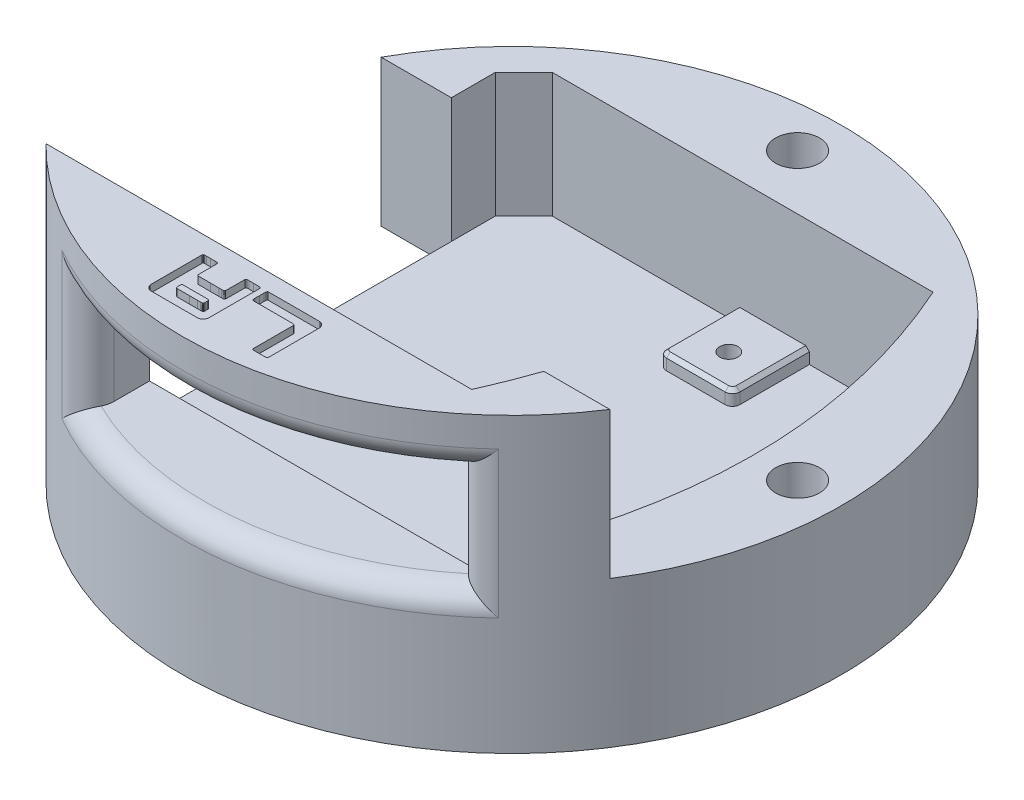
SolidWorks part; units mm, degrees
ref_plane "Plan de face" through (0, 0, 0) normal (0, 0, 1) x (1, 0, 0)
ref_plane "Plan de dessus" through (0, 0, 0) normal (0, 1, 0) x (1, 0, 0)
ref_plane "Plan de droite" through (0, 0, 0) normal (1, 0, 0) x (0, 0, -1)
sketch "Esquisse1" plane through (0, 0, 0) normal (0, 1, 0) x (1, 0, 0)
  circle A0 centre (0, 0) radius 45
  dimension "D1" = 90
extrude "Boss.-Extru.1" add sketch "Esquisse1" along normal blind 40
sketch "Esquisse2" plane through (0, 40, 0) normal (0, 1, 0) x (1, 0, 0)
  line L0 (-26, 31.5) -> (26, 31.5)
  line L1 (26, 0) -> (33, 0) construction
  line L2 (26, 31.5) -> (26, -31.5) construction
  line L3 (-26, 31.5) -> (-29.8891, 27.6109)
  line L4 (-29.8891, 27.6109) -> (-29.8891, 21.6109)
  line L5 (-29.8891, 21.6109) -> (-39.4711, 21.6109)
  line L6 (26, 0) -> (-63.3285, 0) construction
  line L7 (26, 31.5) -> (32.1364, 31.5) construction
  line L8 (-26, 31.5) -> (-32.1364, 31.5) construction
  line L9 (-29.8891, -21.6109) -> (-39.4711, -21.6109)
  line L10 (-29.8891, -27.6109) -> (-29.8891, -21.6109)
  line L11 (-26, -31.5) -> (-29.8891, -27.6109)
  line L12 (-26, -31.5) -> (26, -31.5)
  circle A0 centre (0, 0) radius 45 construction
  arc A1 (-39.4711, -21.6109) -> (-39.4711, 21.6109) centre (0, 0) cw
  spline S0 degree 2 poles (26, 31.5) (40, 0) (26, -31.5) knots 0 0 0 1 1 1
  circle M11 centre (0, 0) radius 45
  dimension "D1" = 52
  dimension "D2" = 7
  dimension "D3" = 63
  dimension "D4" = 135
  dimension "D5" = 5.5
  dimension "D6" = 6
extrude "Enlèv. mat.-Extru.1" cut sketch "Esquisse2" against normal offset from surface (37 mm away) 3 contours S0 L0 L3 L4 L5 L9 L10 L11 L12 M11 region at (-4.3513, 40, 0) up to face at (0, 0, 45)
sketch "Esquisse7" plane through (0, 3, 0) normal (0, 1, 0) x (1, 0, 0)
  line L0 (9.1109, 30) -> (-0.8891, 21) construction
  line L1 (9.1109, 30) -> (9.1109, 22)
  line L2 (8.1109, 21) -> (0.1109, 21)
  line L3 (-0.8891, 30) -> (-0.8891, 22)
  line L4 (-0.8891, 30) -> (9.1109, 30) construction
  line L5 (-0.8891, 30) -> (-0.8891, 31.5)
  line L6 (-0.8891, 31.5) -> (9.1109, 31.5)
  line L7 (9.1109, 30) -> (9.1109, 31.5)
  line L8 (-34.6801, 0) -> (18.839, 0) construction
  line L9 (9.1109, -30) -> (-0.8891, -21) construction
  line L10 (9.1109, -30) -> (9.1109, -31.5)
  line L11 (-0.8891, -31.5) -> (9.1109, -31.5)
  line L12 (-0.8891, -30) -> (-0.8891, -31.5)
  line L13 (-0.8891, -30) -> (-0.8891, -22)
  line L14 (8.1109, -21) -> (0.1109, -21)
  line L15 (9.1109, -30) -> (9.1109, -22)
  line L16 (-34.6801, 21.6109) -> (-34.6801, -21.6109) construction
  line L17 (-26, 31.5) -> (26, 31.5) construction
  line L18 (-29.8891, 21.6109) -> (-39.4711, 21.6109) construction
  arc A0 (0.1109, 21) -> (-0.8891, 22) centre (0.1109, 22) cw
  arc A1 (9.1109, 22) -> (8.1109, 21) centre (8.1109, 22) cw
  arc A2 (9.1109, -22) -> (8.1109, -21) centre (8.1109, -22) ccw
  arc A3 (0.1109, -21) -> (-0.8891, -22) centre (0.1109, -22) ccw
  point P26 (-34.6801, 0)
  point P35 (-34.6801, 21.6109)
  dimension "D2" = 1
  dimension "D1" = 10
  dimension "D3" = 8
  dimension "D4" = 1.5
  dimension "D5" = 33.791
extrude "Boss.-Extru.4" add sketch "Esquisse7" along normal blind 2
chamfer "Chanfrein4" distance 0.5 angle 45 10 edges at (-0.8891, 5, -26.75) (9.1109, 5, -26.75) (-0.5962, 5, -21.2929) (8.818, 5, -21.2929) (4.1109, 5, -21) (9.1109, 5, 26.75) (-0.8891, 5, 26.75) (8.818, 5, 21.2929) (-0.5962, 5, 21.2929) (4.1109, 5, 21)
sketch "Esquisse8" plane through (0, 0, 0) normal (0, -1, 0) x (1, 0, 0)
  line L0 (8.1109, 21.5) -> (0.1109, 21.5) construction
  line L1 (4.1109, 25.5) -> (4.1109, 21.5) construction
  line L2 (0, 0) -> (-4.4948, 0) construction
  circle A0 centre (4.1109, 25.5) radius 1.25
  circle A1 centre (4.1109, -25.5) radius 1.25
  dimension "D1" = 2.5
  dimension "D2" = 4
extrude "Enlèv. mat.-Extru.4" cut sketch "Esquisse8" against normal up to next
chamfer "Chanfrein5" distance 1.5 angle 45 2 edges at (4.1109, 0, -24.25) (4.1109, 0, 24.25)
sketch "Esquisse9" plane through (0, 0, 31.5) normal (0, 0, -1) x (-1, 0, 0)
  line L0 (-26, 33) -> (18, 33)
  line L1 (-26, 33) -> (-26, 19)
  line L2 (-26, 19) -> (18, 19)
  line L3 (18, 33) -> (18, 19)
  line L4 (0.8891, 3) -> (26, 3) construction
  line L5 (-26, 3) -> (-26, 40) construction
  dimension "D1" = 44
  dimension "D2" = 14
  dimension "D3" = 30
extrude "Enlèv. mat.-Extru.5" cut sketch "Esquisse9" against normal up to next
fillet "Congé1" radius 3 4 edges at (26, 26, 36.7287) (4.5929, 33, 44.765) (-18, 26, 41.2432) (4.5929, 19, 44.765)
sketch "Esquisse10" plane through (0, 40, 0) normal (0, 1, 0) x (1, 0, 0)
  line L0 (28.7878, -24.4353) -> (37.7878, -24.4353)
  line L1 (-26, -31.5) -> (-32.1364, -31.5)
  line L2 (-26, -31.5) -> (28.7878, -24.4353)
  arc A0 (-39.4711, -21.6109) -> (-39.4711, 21.6109) centre (0, 0) ccw construction
  arc A1 (-32.1364, -31.5) -> (37.7878, -24.4353) centre (0, 0) cw
  parabola Q5 (26, 31.5) -> (26, -31.5) focus (-2.4375, 0) apex (33, 0) construction
  dimension "D1" = 9
extrude "Enlèv. mat.-Extru.6" cut sketch "Esquisse10" against normal offset from surface (20 mm away) 20 up to face at (4.1109, 0, -22.75)
sketch "Esquisse11" plane through (0, 20, 0) normal (0, 1, 0) x (1, 0, 0)
  line L0 (0, 0) -> (0, 45) construction
  line L1 (0, 0) -> (45, 0) construction
  circle A0 centre (0, 39) radius 1.6
  circle A1 centre (39, 0) radius 1.6
  arc A2 (37.7878, -24.4353) -> (-39.4711, 21.6109) centre (0, 0) ccw construction
  dimension "D1" = 3.2
  dimension "D2" = 3.2
  dimension "D3" = 6
  dimension "D4" = 6
extrude "Enlèv. mat.-Extru.7" cut sketch "Esquisse11" against normal through all
sketch "Esquisse12" plane through (0, 20, 0) normal (0, 1, 0) x (1, 0, 0)
  circle A0 centre (0, 39) radius 3
  circle A1 centre (39, 0) radius 3
  dimension "D1" = 6
  dimension "D2" = 6
extrude "Enlèv. mat.-Extru.8" cut sketch "Esquisse12" against normal blind 10
sketch "Esquisse13" plane through (0, 3, 0) normal (0, 1, 0) x (1, 0, 0)
  line L0 (-29.8891, 21.6109) -> (-29.8891, -21.6109)
  line L1 (-29.8891, -21.6109) -> (-39.4711, -21.6109)
  line L2 (-39.4711, -21.6109) -> (-39.4711, 21.6109) construction
  line L3 (-39.4711, 21.6109) -> (-29.8891, 21.6109)
  arc A0 (-39.4711, 21.6109) -> (-39.4711, -21.6109) centre (0, 0) ccw
extrude "Enlèv. mat.-Extru.9" cut sketch "Esquisse13" against normal up to next
sketch "Esquisse14" plane through (0, 40, 0) normal (0, 1, 0) x (1, 0, 0)
  line L0 (8.3336, -41.5636) -> (8.3347, -40.5342)
  line L1 (8.3343, -38.0353) -> (8.3304, -34.5148)
  line L2 (8.3304, -34.5148) -> (8.3008, -34.4281)
  line L3 (7.7437, -33.8777) -> (7.6504, -33.8481)
  line L4 (7.6504, -33.8481) -> (4.1022, -33.8481)
  line L5 (4.1022, -33.8481) -> (0.5541, -33.8481)
  line L6 (0.5541, -33.8481) -> (0.5063, -33.8845)
  line L7 (0.5227, -35.8917) -> (0.5668, -35.9217)
  line L8 (0.5668, -35.9217) -> (3.3223, -35.9217)
  line L9 (3.3223, -35.9217) -> (6.0778, -35.9217)
  line L10 (6.0778, -35.9217) -> (6.1373, -35.9517)
  line L11 (6.2268, -36.0412) -> (6.2569, -36.1007)
  line L12 (6.2569, -36.1007) -> (6.2569, -38.8562)
  line L13 (6.2569, -38.8562) -> (6.2569, -41.6118)
  line L14 (6.2569, -41.6118) -> (6.2869, -41.6559)
  line L15 (-0.5008, -33.8845) -> (-0.5486, -33.8481)
  line L16 (-0.5486, -33.8481) -> (-1.4297, -33.8443)
  line L17 (-2.4541, -33.9258) -> (-2.4842, -33.9681)
  line L18 (-2.4842, -33.9681) -> (-2.4909, -35.2883)
  line L19 (-2.4909, -35.2883) -> (-2.4976, -36.6084)
  line L20 (-2.4976, -36.6084) -> (-2.5281, -36.6575)
  line L21 (-4.3923, -36.7586) -> (-6.1114, -36.7551)
  line L22 (-6.1114, -36.7551) -> (-6.1563, -36.7231)
  line L23 (-6.2511, -35.2869) -> (-6.2514, -33.992)
  line L24 (-6.2514, -33.992) -> (-6.2814, -33.948)
  line L25 (-8.2975, -33.9399) -> (-8.325, -33.9767)
  line L26 (-8.325, -33.9767) -> (-8.325, -37.5262)
  line L27 (-8.325, -37.5262) -> (-8.325, -41.0756)
  line L28 (-8.325, -41.0756) -> (-8.2954, -41.169)
  line L29 (-7.7449, -41.7261) -> (-7.6582, -41.7557)
  line L30 (-7.6582, -41.7557) -> (-4.4045, -41.7581)
  line L31 (-6.1563, -38.8807) -> (-6.1114, -38.8487)
  line L32 (-6.1114, -38.8487) -> (-4.3923, -38.8452)
  line L33 (-4.3717, -39.6821) -> (-6.0724, -39.6821)
  line L34 (-6.0724, -39.6821) -> (-6.1319, -39.6521)
  arc A0 (8.2111, -41.7438) -> (8.2503, -41.7196) centre (8.1444, -41.5919) ccw
  arc A1 (8.2503, -41.7196) -> (8.2873, -41.6824) centre (8.0739, -41.507) ccw
  arc A2 (8.2873, -41.6824) -> (8.3161, -41.6396) centre (8.08, -41.5119) ccw
  arc A3 (8.3161, -41.6396) -> (8.3304, -41.5987) centre (8.1957, -41.5745) ccw
  arc A4 (8.3304, -41.5987) -> (8.3336, -41.5636) centre (8.1333, -41.5633) ccw
  arc A5 (8.3347, -40.5342) -> (8.3352, -39.3881) centre (-841.87, -39.6126) ccw
  arc A6 (8.3352, -39.3881) -> (8.3343, -38.0353) centre (-1633.4732, -39.822) ccw
  arc A7 (8.3008, -34.4281) -> (8.2131, -34.2445) centre (7.4674, -34.7132) ccw
  arc A8 (8.2131, -34.2445) -> (8.0855, -34.0854) centre (7.4612, -34.7171) ccw
  arc A9 (8.0855, -34.0854) -> (7.9258, -33.9606) centre (7.4691, -34.7091) ccw
  arc A10 (7.9258, -33.9606) -> (7.7437, -33.8777) centre (7.4923, -34.6712) ccw
  arc A11 (0.5063, -33.8845) -> (0.4515, -33.9549) centre (0.6125, -34.0238) ccw
  arc A12 (0.4515, -33.9549) -> (0.426, -34.0571) centre (0.7557, -34.0851) ccw
  arc A13 (0.426, -34.0571) -> (0.4175, -34.2554) centre (2.7542, -34.2551) ccw
  arc A14 (0.4175, -34.2554) -> (0.419, -34.9106) centre (156.8501, -34.2344) ccw
  arc A15 (0.419, -34.9106) -> (0.422, -35.4849) centre (327.504, -33.4972) ccw
  arc A16 (0.422, -35.4849) -> (0.4259, -35.6777) centre (7.164, -35.444) ccw
  arc A17 (0.4259, -35.6777) -> (0.4331, -35.7791) centre (1.8243, -35.6292) ccw
  arc A18 (0.4331, -35.7791) -> (0.4507, -35.824) centre (0.5246, -35.7693) ccw
  arc A19 (0.4507, -35.824) -> (0.4645, -35.8406) centre (0.6004, -35.713) ccw
  arc A20 (0.4645, -35.8406) -> (0.4833, -35.8594) centre (0.774, -35.5501) ccw
  arc A21 (0.4833, -35.8594) -> (0.5038, -35.8774) centre (0.7829, -35.5406) ccw
  arc A22 (0.5038, -35.8774) -> (0.5227, -35.8917) centre (0.6636, -35.6845) ccw
  arc A23 (6.1669, -35.9691) -> (6.1373, -35.9517) centre (6.0187, -36.1869) ccw
  arc A24 (6.1902, -35.9883) -> (6.1669, -35.9691) centre (6.0763, -36.1022) ccw
  arc A25 (6.2095, -36.0117) -> (6.1902, -35.9883) centre (6.0763, -36.1022) ccw
  arc A26 (6.2268, -36.0412) -> (6.2095, -36.0117) centre (5.9916, -36.1598) ccw
  arc A27 (6.2869, -41.6559) -> (6.3011, -41.6748) centre (6.494, -41.5149) ccw
  arc A28 (6.3011, -41.6748) -> (6.3191, -41.6952) centre (6.6379, -41.3956) ccw
  arc A29 (6.3191, -41.6952) -> (6.3379, -41.714) centre (6.6283, -41.4046) ccw
  arc A30 (6.3379, -41.714) -> (6.3545, -41.7278) centre (6.4655, -41.5781) ccw
  arc A31 (6.3545, -41.7278) -> (6.3996, -41.7454) centre (6.4092, -41.654) ccw
  arc A32 (6.3996, -41.7454) -> (6.5022, -41.7525) centre (6.55, -40.319) ccw
  arc A33 (6.5022, -41.7525) -> (6.6973, -41.7562) centre (6.7322, -34.8454) ccw
  arc A34 (6.6973, -41.7562) -> (7.2813, -41.7587) centre (8.4138, 298.5438) ccw
  arc A35 (7.2813, -41.7587) -> (7.7496, -41.7595) centre (7.7994, 113.931) ccw
  arc A36 (7.7496, -41.7595) -> (8.0034, -41.7576) centre (7.7546, -26.229) ccw
  arc A37 (8.0034, -41.7576) -> (8.1674, -41.7537) centre (7.8312, -31.0139) ccw
  arc A38 (8.1674, -41.7537) -> (8.2111, -41.7438) centre (8.1637, -41.636) ccw
  arc A39 (-1.068, -41.7424) -> (-0.9412, -41.7017) centre (-1.217, -41.0597) ccw
  arc A40 (-0.9412, -41.7017) -> (-0.8145, -41.6353) centre (-1.3068, -40.8508) ccw
  arc A41 (-0.8145, -41.6353) -> (-0.698, -41.5491) centre (-1.3195, -40.8305) ccw
  arc A42 (-0.698, -41.5491) -> (-0.6013, -41.4495) centre (-1.2221, -40.9431) ccw
  arc A43 (-0.6013, -41.4495) -> (-0.5559, -41.3871) centre (-1.1275, -41.0203) ccw
  arc A44 (-0.5559, -41.3871) -> (-0.5127, -41.3131) centre (-1.4204, -40.8323) ccw
  arc A45 (-0.5127, -41.3131) -> (-0.474, -41.2323) centre (-1.4999, -40.7902) ccw
  arc A46 (-0.474, -41.2323) -> (-0.4421, -41.149) centre (-1.4788, -40.7993) ccw
  arc A47 (-0.4421, -41.149) -> (-0.4255, -41.0529) centre (-0.7411, -41.0481) ccw
  arc A48 (-0.4255, -41.0529) -> (-0.4202, -40.5962) centre (-62.4465, -40.1056) ccw
  arc A49 (-0.4202, -40.5962) -> (-0.4165, -39.7961) centre (-125.2051, -39.6091) ccw
  arc A50 (-0.4165, -39.7961) -> (-0.4136, -37.5552) centre (-4958.0687, -32.364) ccw
  arc A51 (-0.4136, -37.5552) -> (-0.4116, -34.8688) centre (-4418.828, -32.926) ccw
  arc A52 (-0.4116, -34.8688) -> (-0.4185, -34.2772) centre (-24.8776, -34.8581) ccw
  arc A53 (-0.4185, -34.2772) -> (-0.4388, -33.993) centre (-3.4147, -34.3483) ccw
  arc A54 (-0.4388, -33.993) -> (-0.5008, -33.8845) centre (-0.5981, -34.0121) ccw
  arc A55 (-1.4297, -33.8443) -> (-2.0823, -33.8429) centre (-2.098, -191.4752) ccw
  arc A56 (-2.0823, -33.8429) -> (-2.2852, -33.851) centre (-2.0826, -36.3993) ccw
  arc A57 (-2.2852, -33.851) -> (-2.3884, -33.8747) centre (-2.2564, -34.2128) ccw
  arc A58 (-2.3884, -33.8747) -> (-2.4541, -33.9258) centre (-2.3355, -34.0104) ccw
  arc A59 (-2.5443, -36.6791) -> (-2.5281, -36.6575) centre (-2.6594, -36.5758) ccw
  arc A60 (-2.5661, -36.7006) -> (-2.5443, -36.6791) centre (-2.7327, -36.51) ccw
  arc A61 (-2.5908, -36.7197) -> (-2.5661, -36.7006) centre (-2.739, -36.5028) ccw
  arc A62 (-2.6159, -36.7343) -> (-2.5908, -36.7197) centre (-2.7012, -36.5581) ccw
  arc A63 (-2.687, -36.7523) -> (-2.6159, -36.7343) centre (-2.6954, -36.5701) ccw
  arc A64 (-2.8814, -36.7582) -> (-2.687, -36.7523) centre (-2.9632, -30.7765) ccw
  arc A65 (-3.2474, -36.7604) -> (-2.8814, -36.7582) centre (-3.2177, -12.1526) ccw
  arc A66 (-4.3923, -36.7586) -> (-3.2474, -36.7604) centre (-1.564, 1359.5283) ccw
  arc A67 (-6.1753, -36.7069) -> (-6.1563, -36.7231) centre (-6.0726, -36.6058) ccw
  arc A68 (-6.1952, -36.6844) -> (-6.1753, -36.7069) centre (-5.9615, -36.4964) ccw
  arc A69 (-6.2132, -36.6597) -> (-6.1952, -36.6844) centre (-5.9561, -36.492) ccw
  arc A70 (-6.226, -36.6364) -> (-6.2132, -36.6597) centre (-6.0662, -36.5639) ccw
  arc A71 (-6.2414, -36.5728) -> (-6.226, -36.6364) centre (-6.0662, -36.5639) ccw
  arc A72 (-6.2473, -36.4048) -> (-6.2414, -36.5728) centre (-1.0597, -36.3083) ccw
  arc A73 (-6.2504, -36.1005) -> (-6.2473, -36.4048) centre (11.5933, -36.0728) ccw
  arc A74 (-6.2511, -35.2869) -> (-6.2504, -36.1005) centre (606.421, -35.1486) ccw
  arc A75 (-6.2814, -33.948) -> (-6.2956, -33.929) centre (-6.4884, -34.0888) ccw
  arc A76 (-6.2956, -33.929) -> (-6.3136, -33.9086) centre (-6.6323, -34.2081) ccw
  arc A77 (-6.3136, -33.9086) -> (-6.3324, -33.8898) centre (-6.6228, -34.1992) ccw
  arc A78 (-6.3324, -33.8898) -> (-6.349, -33.876) centre (-6.46, -34.0257) ccw
  arc A79 (-6.349, -33.876) -> (-6.3943, -33.8584) centre (-6.4036, -33.9496) ccw
  arc A80 (-6.3943, -33.8584) -> (-6.4978, -33.8517) centre (-6.5407, -35.2993) ccw
  arc A81 (-6.4978, -33.8517) -> (-6.695, -33.8486) centre (-6.7067, -40.9083) ccw
  arc A82 (-6.695, -33.8486) -> (-7.2915, -33.8481) centre (-7.2912, -393.2007) ccw
  arc A83 (-7.2915, -33.8481) -> (-7.8847, -33.8486) centre (-7.2913, -386.0898) ccw
  arc A84 (-7.8847, -33.8486) -> (-8.0836, -33.8516) centre (-7.8725, -41.0822) ccw
  arc A85 (-8.0836, -33.8516) -> (-8.1885, -33.8583) centre (-8.0385, -35.3954) ccw
  arc A86 (-8.1885, -33.8583) -> (-8.2332, -33.8756) centre (-8.1799, -33.947) ccw
  arc A87 (-8.2332, -33.8756) -> (-8.2493, -33.8888) centre (-8.0952, -34.0603) ccw
  arc A88 (-8.2493, -33.8888) -> (-8.2672, -33.9058) centre (-7.9414, -34.2316) ccw
  arc A89 (-8.2672, -33.9058) -> (-8.2843, -33.9238) centre (-7.9414, -34.2316) ccw
  arc A90 (-8.2843, -33.9238) -> (-8.2975, -33.9399) centre (-8.1127, -34.0778) ccw
  arc A91 (-8.2954, -41.169) -> (-8.2124, -41.3515) centre (-7.4953, -40.9155) ccw
  arc A92 (-8.2124, -41.3515) -> (-8.0879, -41.511) centre (-7.4692, -40.8996) ccw
  arc A93 (-8.0879, -41.511) -> (-7.929, -41.6383) centre (-7.4611, -40.8916) ccw
  arc A94 (-7.929, -41.6383) -> (-7.7449, -41.7261) centre (-7.4574, -40.8858) ccw
  arc A95 (-4.4045, -41.7581) -> (-2.6497, -41.7587) centre (-2.7092, 2304.2614) ccw
  arc A96 (-2.6497, -41.7587) -> (-1.7515, -41.7566) centre (-2.6547, 149.9899) ccw
  arc A97 (-1.7515, -41.7566) -> (-1.1629, -41.753) centre (-2.7432, 168.7567) ccw
  arc A98 (-1.1629, -41.753) -> (-1.068, -41.7424) centre (-1.1664, -41.2915) ccw
  arc A99 (-6.1614, -39.6348) -> (-6.1319, -39.6521) centre (-6.0133, -39.4169) ccw
  arc A100 (-6.1847, -39.6155) -> (-6.1614, -39.6348) centre (-6.0709, -39.5016) ccw
  arc A101 (-6.204, -39.5922) -> (-6.1847, -39.6155) centre (-6.0709, -39.5016) ccw
  arc A102 (-6.2214, -39.5626) -> (-6.204, -39.5922) centre (-5.9862, -39.444) ccw
  arc A103 (-6.2381, -39.5202) -> (-6.2214, -39.5626) centre (-5.9976, -39.4498) ccw
  arc A104 (-6.2468, -39.4756) -> (-6.2381, -39.5202) centre (-6.0036, -39.4515) ccw
  arc A105 (-6.2504, -39.4082) -> (-6.2468, -39.4756) centre (-5.4887, -39.4006) ccw
  arc A106 (-6.2511, -39.2626) -> (-6.2504, -39.4082) centre (6.6941, -39.2784) ccw
  arc A107 (-6.2476, -39.0858) -> (-6.2511, -39.2626) centre (-1.5054, -39.2684) ccw
  arc A108 (-6.2342, -38.9915) -> (-6.2476, -39.0858) centre (-5.7823, -39.1037) ccw
  arc A109 (-6.206, -38.9304) -> (-6.2342, -38.9915) centre (-6.0604, -39.0346) ccw
  arc A110 (-6.1563, -38.8807) -> (-6.206, -38.9304) centre (-6.032, -39.055) ccw
  arc A111 (-3.2474, -38.8434) -> (-4.3923, -38.8452) centre (-1.564, -1435.1321) ccw
  arc A112 (-2.8814, -38.8456) -> (-3.2474, -38.8434) centre (-3.2177, -63.4512) ccw
  arc A113 (-2.687, -38.8515) -> (-2.8814, -38.8456) centre (-2.9632, -44.8273) ccw
  arc A114 (-2.6159, -38.8695) -> (-2.687, -38.8515) centre (-2.6954, -39.0337) ccw
  arc A115 (-2.5908, -38.8841) -> (-2.6159, -38.8695) centre (-2.7012, -39.0457) ccw
  arc A116 (-2.5661, -38.9032) -> (-2.5908, -38.8841) centre (-2.739, -39.101) ccw
  arc A117 (-2.5443, -38.9247) -> (-2.5661, -38.9032) centre (-2.7327, -39.0938) ccw
  arc A118 (-2.5281, -38.9463) -> (-2.5443, -38.9247) centre (-2.6594, -39.028) ccw
  arc A119 (-2.5107, -38.9839) -> (-2.5281, -38.9463) centre (-2.6722, -39.0359) ccw
  arc A120 (-2.5019, -39.0263) -> (-2.5107, -38.9839) centre (-2.7022, -39.0456) ccw
  arc A121 (-2.4983, -39.0952) -> (-2.5019, -39.0263) centre (-3.2845, -39.1019) ccw
  arc A122 (-2.4976, -39.2621) -> (-2.4983, -39.0952) centre (-22.0355, -39.2621) ccw
  arc A123 (-2.4983, -39.4287) -> (-2.4976, -39.2621) centre (-21.9238, -39.2621) ccw
  arc A124 (-2.5019, -39.4977) -> (-2.4983, -39.4287) centre (-3.2907, -39.4219) ccw
  arc A125 (-2.5106, -39.5401) -> (-2.5019, -39.4977) centre (-2.7041, -39.4783) ccw
  arc A126 (-2.5279, -39.5776) -> (-2.5106, -39.5401) centre (-2.6701, -39.4892) ccw
  arc A127 (-2.5438, -39.5987) -> (-2.5279, -39.5776) centre (-2.6545, -39.4988) ccw
  arc A128 (-2.5657, -39.6204) -> (-2.5438, -39.5987) centre (-2.7467, -39.4157) ccw
  arc A129 (-2.5903, -39.6398) -> (-2.5657, -39.6204) centre (-2.7521, -39.4096) ccw
  arc A130 (-2.6146, -39.6542) -> (-2.5903, -39.6398) centre (-2.6965, -39.4887) ccw
  arc A131 (-2.6846, -39.6724) -> (-2.6146, -39.6542) centre (-2.6932, -39.4954) ccw
  arc A132 (-2.8772, -39.6786) -> (-2.6846, -39.6724) centre (-2.9707, -33.7894) ccw
  arc A133 (-3.2396, -39.6816) -> (-2.8772, -39.6786) centre (-3.2599, -15.5832) ccw
  arc A134 (-4.3717, -39.6821) -> (-3.2396, -39.6816) centre (-4.3808, 1320.9145) ccw
extrude "Signature" cut sketch "Esquisse14" against normal blind 1
